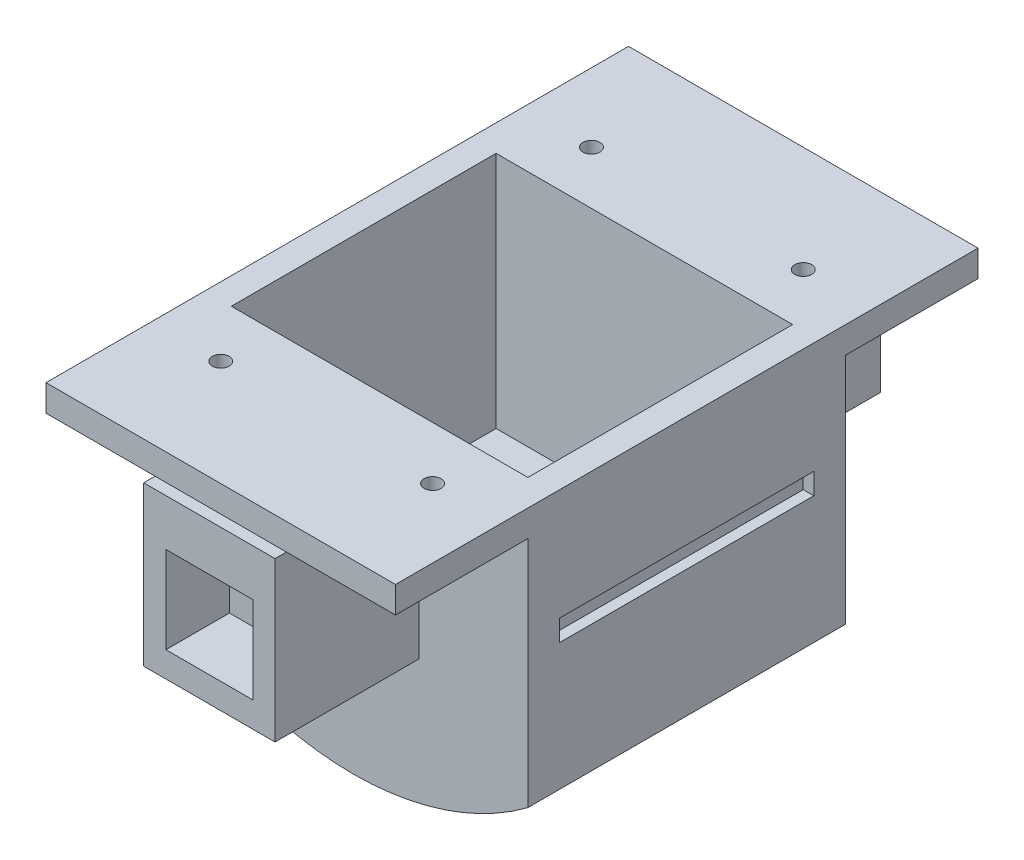
SolidWorks part; units mm, degrees
ref_plane "Front Plane" through (0, 0, 0) normal (0, 0, 1) x (1, 0, 0)
ref_plane "Top Plane" through (0, 0, 0) normal (0, 1, 0) x (1, 0, 0)
ref_plane "Right Plane" through (0, 0, 0) normal (1, 0, 0) x (0, 0, -1)
sketch "Sketch1" plane through (0, 0, 0) normal (0, 0, 1) x (1, 0, 0)
  line L0 (0, 0) -> (0, -42) construction
  line L1 (0, 0) -> (55, 0)
  line L2 (55, 0) -> (-55, 0)
  arc A0 (-55, 0) -> (55, 0) centre (0, 0) ccw
  dimension "D2" = 55
  dimension "D1" = 42
extrude "Boss-Extrude1" add sketch "Sketch1" along normal blind 30 and the other way blind 30 contours L2 A0 L1 region at (0, -23.3427, 0)
sketch "Sketch2" plane through (0, 0, 0) normal (0, 0, 1) x (1, 0, 0)
  line L1 (0, 0) -> (-9.5, 0)
  line L3 (2.8861, -52) -> (-9.5, -52)
  line L4 (-9.5, 0) -> (-9.5, -52)
  line L5 (0, 0) -> (9.5, 0)
  line L7 (2.8861, -52) -> (9.5, -52)
  line L8 (9.5, 0) -> (9.5, -52)
  circle A0 centre (0, 0) radius 42
  dimension "D1" = 84
  dimension "D2" = 9.5
  dimension "D3" = 9.5
  dimension "D4" = 52
extrude "Cut-Extrude1" cut sketch "Sketch2" against normal blind 18 and the other way blind 18 contours L4 A0 L8 L5 L1 | A0 L4 L3 | A0 L3 L7 L8 region at (0, -20.8208, 0) region at (0, -46.8145, 0)
sketch "Sketch3" plane through (0, 0, 30) normal (0, 0, 1) x (1, 0, 0)
  line L0 (0, 0) -> (0, -28.5435) construction
  line L1 (-54.8544, -4) -> (-33, -4)
  line L2 (-54.8544, -4) -> (-54.8544, -49)
  line L3 (-54.8544, -49) -> (-33, -49)
  line L4 (-33, -4) -> (-33, -49)
  line L5 (55, 0) -> (-55, 0) construction
  line L6 (33, -4) -> (33, -49)
  line L7 (54.8544, -49) -> (33, -49)
  line L8 (54.8544, -4) -> (54.8544, -49)
  line L9 (54.8544, -4) -> (33, -4)
  arc A0 (-55, 0) -> (55, 0) centre (0, 0) ccw construction
  dimension "D1" = 4
  dimension "D2" = 33
  dimension "D3" = 45
extrude "Cut-Extrude2" cut sketch "Sketch3" against normal through all
sketch "Sketch4" plane through (0, 0, 0) normal (0, 1, 0) x (1, 0, 0)
  line L0 (55, 30) -> (-55, 30) construction
  line L1 (55, 30) -> (55, -30) construction
  line L2 (0, 0) -> (0, 55.9923) construction
  line L3 (0, 0) -> (36.0907, 0) construction
  circle A0 centre (45, 20) radius 1.6
  circle A1 centre (45, -20) radius 1.6
  circle A2 centre (-45, -20) radius 1.6
  circle A3 centre (-45, 20) radius 1.6
  dimension "D1" = 3.2
  dimension "D2" = 10
  dimension "D3" = 10
extrude "Cut-Extrude3" cut sketch "Sketch4" against normal through all
sketch "Sketch6" plane through (33, 0, 0) normal (1, 0, 0) x (0, 0, -1)
  line L0 (-30, -4) -> (-30, -44) construction
  line L1 (-24, -16) -> (24, -16)
  line L2 (-24, -16) -> (-24, -20)
  line L3 (-24, -20) -> (24, -20)
  line L4 (24, -16) -> (24, -20)
  line L5 (30, -4) -> (30, -44) construction
  line L6 (30, -4) -> (-30, -4) construction
  dimension "D1" = 6
  dimension "D2" = 6
  dimension "D3" = 12
  dimension "D4" = 4
extrude "Cut-Extrude5" cut sketch "Sketch6" against normal blind 2
sketch "Sketch9" plane through (0, 0, 0) normal (0, 1, 0) x (1, 0, 0)
  line L5 (-55, 30) -> (-33, 30)
  line L6 (-55, 30) -> (-55, -30)
  line L7 (-55, -30) -> (-33, -30)
  line L8 (-33, 30) -> (-33, -30)
  line L9 (55, 30) -> (33, 30)
  line L10 (55, 30) -> (55, -30)
  line L11 (55, -30) -> (33, -30)
  line L12 (33, 30) -> (33, -30)
extrude "Cut-Extrude7" cut sketch "Sketch9" against normal through all
sketch "Sketch10" plane through (0, 0, 0) normal (0, 1, 0) x (1, 0, 0)
  line L1 (-33, 30) -> (33, 30)
  line L2 (-33, 30) -> (-33, -30)
  line L3 (-33, -30) -> (33, -30)
  line L4 (33, 30) -> (33, -30)
  line L5 (33, -30) -> (-33, -30)
  line L6 (33, -30) -> (33, -55)
  line L7 (33, -55) -> (-33, -55)
  line L8 (-33, -30) -> (-33, -55)
  line L9 (-33, 30) -> (33, 30)
  line L10 (-33, 30) -> (-33, 55)
  line L11 (-33, 55) -> (33, 55)
  line L12 (33, 30) -> (33, 55)
  line L13 (-9.5, 18) -> (9.5, 18)
  line L14 (-9.5, 18) -> (-9.5, -18)
  line L15 (-9.5, -18) -> (9.5, -18)
  line L16 (9.5, 18) -> (9.5, -18)
  line M3 (-33, 30) -> (-33, -30)
  line M4 (-33, -30) -> (33, -30)
  line M5 (33, -30) -> (33, 30)
  line M6 (33, 30) -> (-33, 30)
  line M7 (9.5, -18) -> (-9.5, -18)
  line M8 (-9.5, -18) -> (-9.5, 18)
  line M9 (-9.5, 18) -> (9.5, 18)
  line M10 (9.5, 18) -> (9.5, -18)
  dimension "D1" = 25
  dimension "D2" = 25
extrude "Boss-Extrude2" add sketch "Sketch10" along normal blind 5 contours L12 L11 L10 M6 | M6 M3 M4 M5 M10 M7 M8 M9 | L8 L7 L6 M4 region at (0, 0, -42.5) region at (0, 0, -29.108) region at (0, 0, 42.5)
sketch "Sketch11" plane through (0, 5, 0) normal (0, 1, 0) x (1, 0, 0)
  line L0 (0, 0) -> (-22.9202, 0) construction
  line L1 (-22.9202, 0) -> (0, 0) construction
  circle A0 centre (-20, 35) radius 1.6
  circle A1 centre (20, 35) radius 1.6
  circle A2 centre (-20, -35) radius 1.6
  circle A3 centre (20, -35) radius 1.6
  dimension "D1" = 3.2
  dimension "D2" = 35
  dimension "D3" = 20
  dimension "D5" = 40
  dimension "D4" = 2
extrude "Cut-Extrude8" cut sketch "Sketch11" against normal through all
sketch "Sketch13" plane through (0, 0, -30) normal (0, 0, -1) x (-1, 0, 0)
  line L0 (33, 0) -> (-33, 0) construction
  line L11 (-18.4, 0) -> (-18.4, 5) construction
  line L12 (-12.4, 0) -> (12.4, 0)
  line L13 (-12.4, 0) -> (-12.4, -30)
  line L14 (-12.4, -30) -> (12.4, -30)
  line L15 (12.4, 0) -> (12.4, -30)
  line L16 (18.4, 5) -> (18.4, 0) construction
  point P0 (0, -17)
  dimension "D5" = 6
  dimension "D6" = 30
  dimension "D7" = 6
extrude "Boss-Extrude3" add sketch "Sketch13" along normal blind 27.15
sketch "Sketch14" plane through (0, 0, -57.15) normal (0, 0, -1) x (-1, 0, 0)
  line L0 (33, -44) -> (33, 0) construction
  line L5 (33, 0) -> (12.4, 0) construction
  line L6 (0, -17) -> (0, 0) construction
  line L7 (-8, -9) -> (8, -9)
  line L8 (-8, -9) -> (-8, -25)
  line L9 (-8, -25) -> (8, -25)
  line L10 (8, -9) -> (8, -25)
  line L11 (-8, -9) -> (8, -25) construction
  line L12 (-8, -25) -> (8, -9) construction
  line L14 (-8.2, -8.8) -> (8.2, -8.8)
  line L15 (-8.2, -8.8) -> (-8.2, -25.2)
  line L16 (-8.2, -25.2) -> (8.2, -25.2)
  line L17 (8.2, -8.8) -> (8.2, -25.2)
  line L18 (-8.2, -8.8) -> (8.2, -25.2) construction
  line L19 (-8.2, -25.2) -> (8.2, -8.8) construction
  point P4 (0, -17)
  dimension "D1" = 16
  dimension "D2" = 9
  dimension "D3" = 16
  dimension "D4" = 25
  dimension "D5" = 17
  dimension "D6" = 0.2
  dimension "D7" = 0.2
extrude "Cut-Extrude9" cut sketch "Sketch14" against normal blind 12 contours L10 L7 L8 L9 | L17 L14 L15 L16 L7 L10 L9 L8 region at (0, -17, -57.15) region at (0, -8.8232, -57.15)
ref_plane "Plane1" through (0, 0, 0) normal (0, 0, -1) x (-1, 0, 0)
mirror "Mirror2" about plane through (0, 0, 0) normal (0, 0, -1) of "Boss-Extrude3"
mirror "Mirror3" about plane through (0, 0, 0) normal (0, 0, -1) of "Cut-Extrude9"
sketch "Sketch15" plane through (0, 5, 0) normal (0, 1, 0) x (1, 0, 0)
  line L0 (-12.4, 30) -> (-33, 30) construction
  line L1 (-28, 25) -> (28, 25)
  line L2 (-28, 25) -> (-28, -25)
  line L3 (-28, -25) -> (28, -25)
  line L4 (28, 25) -> (28, -25)
  line L5 (-12.4, -30) -> (-33, -30) construction
  line L6 (-33, -55) -> (-33, 55) construction
  line L7 (33, -55) -> (33, 55) construction
  dimension "D1" = 5
  dimension "D2" = 5
  dimension "D3" = 5
  dimension "D4" = 5
extrude "Cut-Extrude10" cut sketch "Sketch15" against normal blind 45
